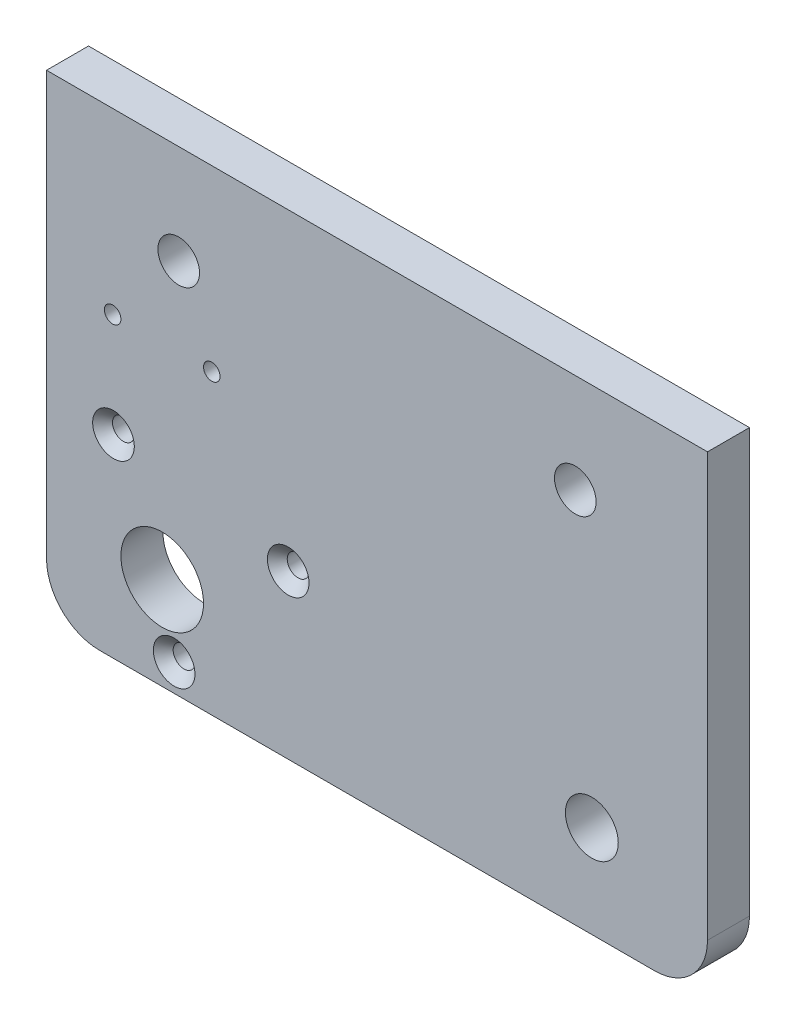
SolidWorks part; units mm, degrees
ref_plane "Front Plane" through (0, 0, 0) normal (0, 0, 1) x (1, 0, 0)
ref_plane "Top Plane" through (0, 0, 0) normal (0, 1, 0) x (1, 0, 0)
ref_plane "Right Plane" through (0, 0, 0) normal (1, 0, 0) x (0, 0, -1)
sketch "Sketch2" plane through (0, 0, 0) normal (0, 0, 1) x (1, 0, 0)
  line L1 (0, 0) -> (100, 0)
  line L2 (0, 0) -> (0, 72)
  line L3 (0, 72) -> (100, 72)
  line L4 (100, 0) -> (100, 72)
  dimension "D1" = 72
  dimension "D2" = 100
extrude "Boss-Extrude1" add sketch "Sketch2" along normal blind 6.35
fillet "Fillet1" radius 8 2 edges at (100, 0, 3.175) (0, 0, 3.175)
sketch "Sketch4" plane through (0, 0, 0) normal (0, 0, 1) x (1, 0, 0)
  line L0 (8, 0) -> (92, 0) construction
  line L1 (25, 45) -> (10, 45) construction
  line L3 (0, 72) -> (0, 8) construction
  line L4 (100, 72) -> (0, 72) construction
  line L5 (20, 57) -> (80, 57) construction
  circle A0 centre (17.5, 14) radius 6.25
  circle A1 centre (82.5, 14) radius 4
  circle A2 centre (20, 57) radius 3.15
  circle A3 centre (80, 57) radius 3.15
  circle A4 centre (10, 45) radius 1.25
  circle A5 centre (25, 45) radius 1.25
  point P14 (50, 57)
  point P15 (50, 72)
  point P20 (17.5, 45)
  dimension "D1" = 14
  dimension "D3" = 12.5
  dimension "D4" = 8
  dimension "D6" = 15
  dimension "D9" = 6.3
  dimension "D10" = 2.5
  dimension "D2" = 65
  dimension "D5" = 17.5
  dimension "D7" = 15
  dimension "D8" = 60
  dimension "D11" = 31
  dimension "D12" = 15
extrude "Cut-Extrude9" cut sketch "Sketch4" along normal through all
sketch "Sketch5" plane through (0, 0, 6.35) normal (0, 0, 1) x (1, 0, 0)
  line L0 (10.1263, 29.3251) -> (36.5652, 24.6632) construction
  line L1 (36.5652, 24.6632) -> (19.3085, 4.0974) construction
  line L2 (19.3085, 4.0974) -> (10.1263, 29.3251) construction
  line L3 (22, 19.3619) -> (19.3085, 4.0974) construction
  line L4 (22, 19.3619) -> (22, 3.8619) construction
  circle A0 centre (22, 19.3619) radius 15.5 construction
  circle A2 centre (10.1263, 29.3251) radius 1.65
  circle A3 centre (36.5652, 24.6632) radius 1.65
  circle A4 centre (19.3085, 4.0974) radius 1.65
  dimension "D1" = 7
  dimension "D3" = 31
  dimension "D4" = 3.3
  dimension "D2" = 4.5
  dimension "D5" = 10
extrude "Cut-Extrude11" cut sketch "Sketch5" against normal through all
chamfer "Chamfer1" distance 1.5 angle 45 6 edges at (20.9585, 4.0974, 6.35) (38.2152, 24.6632, 6.35) (11.7763, 29.3251, 6.35) (20.9585, 4.0974, 0) (11.7763, 29.3251, 0) (38.2152, 24.6632, 0)
ref_axis "Axis1" through (10.1263, 29.3251, 1.5) along (0, 0, 1)
ref_axis "Axis2" through (17.5, 14, 37.9963) along (0, 0, -1)
ref_plane "Plane1" through (19.6801, 9.4691, 0) normal (0.9011, 0.4336, 0) x (0, 0, -1)
